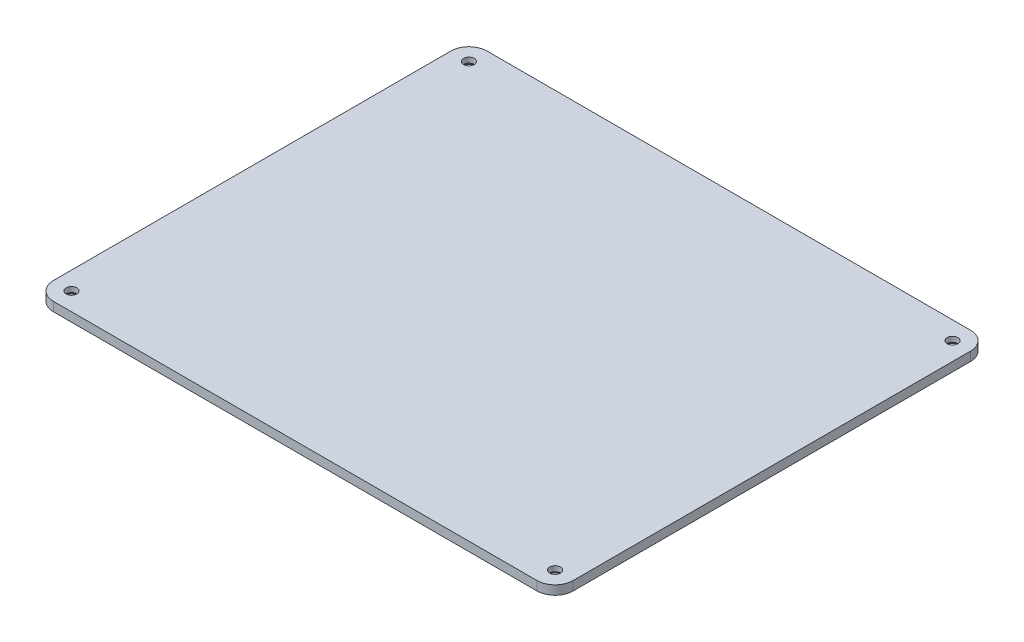
SolidWorks part; units mm, degrees
material "ABS"
ref_plane "Front" through (0, 0, 0) normal (0, 0, 1) x (1, 0, 0)
ref_plane "Top" through (0, 0, 0) normal (0, 1, 0) x (1, 0, 0)
ref_plane "Right" through (0, 0, 0) normal (1, 0, 0) x (0, 0, -1)
sketch "Sketch1" plane through (0, 0, 0) normal (0, 1, 0) x (1, 0, 0)
  line L1 (-43.1005, 35.9565) -> (43.1005, 35.9565)
  line L2 (-43.1005, 35.9565) -> (-43.1005, -35.9565)
  line L3 (-43.1005, -35.9565) -> (43.1005, -35.9565)
  line L4 (43.1005, 35.9565) -> (43.1005, -35.9565)
  line L5 (-43.1005, 35.9565) -> (43.1005, -35.9565) construction
  line L6 (-43.1005, -35.9565) -> (43.1005, 35.9565) construction
  point P0 (0, 0)
  dimension "D1" = 71.913
  dimension "D2" = 86.201
extrude "Boss-Extrude1" add sketch "Sketch1" along normal blind 1.5
fillet "Fillet1" radius 3 4 edges at (-43.1005, 0.75, 35.9565) (-43.1005, 0.75, -35.9565) (43.1005, 0.75, -35.9565) (43.1005, 0.75, 35.9565)
hole_wizard "#2-56 Tapped Hole1" positions "Sketch2" profile "Sketch4" tap size "#2-56" standard "ANSI Inch" end condition through all
sketch "Sketch2" plane through (0, 0, 0) normal (0, -1, 0) x (-1, 0, 0)
  point P0 (40.1005, -32.9565)
  point P3 (-40.1005, -32.9565)
  point P6 (-40.1005, 32.9565)
  point P9 (40.1005, 32.9565)
sketch "Sketch4" plane through (-40.1005, 0, 32.9565) normal (1, 0, 0) x (0, 0, -1)
  line L0 (0, 0) -> (0, 1.5)
  line L1 (0, 1.5) -> (0.889, 1.5)
  line L2 (0.889, 1.5) -> (0.889, 0.635)
  line L3 (0.889, 0.635) -> (1.524, 0)
  line L5 (1.524, 0) -> (0, 0)
  line L6 (-0.889, 0.635) -> (-1.524, 0) construction
  line L11 (0, -6.35) -> (0, 107.95) construction
  dimension "Thru Tap Drill Dia." = 1.778
  dimension "Thru Tap Drill Depth" = 1.5
  dimension "Near C'Sink Dia." = 3.048
  dimension "Near C'Sink Angle" = 90
cosmetic thread "Hole Thread1" parameters "D2"=2.1844
cosmetic thread "Hole Thread2" parameters "D2"=2.1844
cosmetic thread "Hole Thread3" parameters "D2"=2.1844
cosmetic thread "Hole Thread4" parameters "D2"=2.1844
